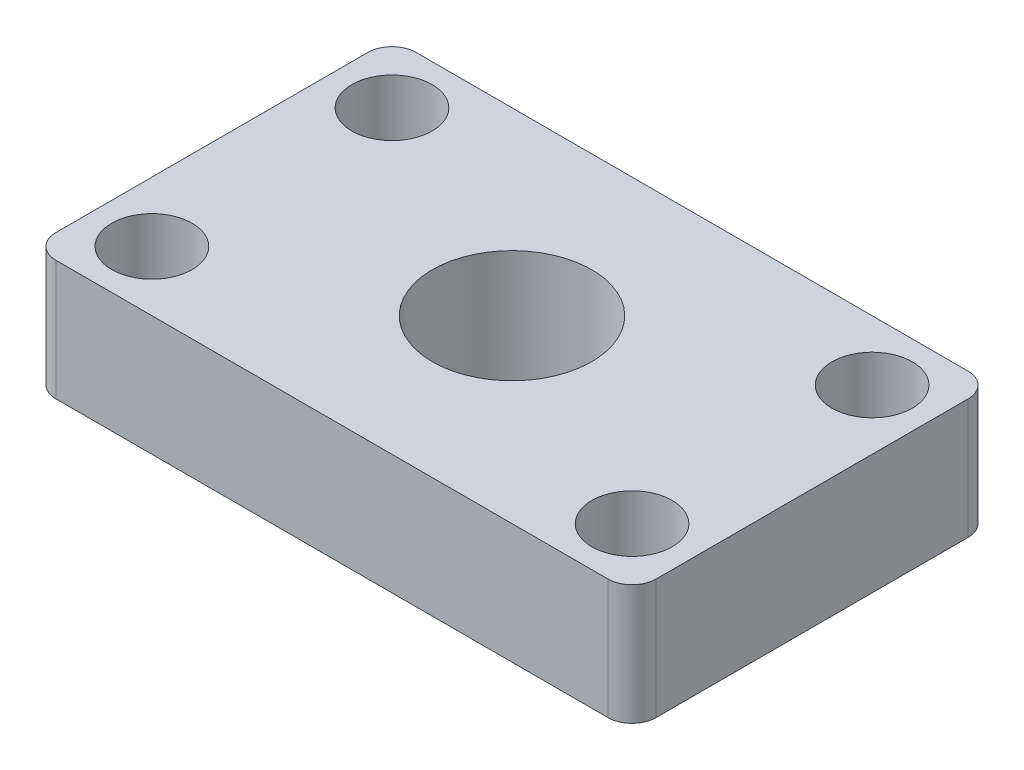
SolidWorks part; units mm, degrees
ref_plane "Front Plane" through (0, 0, 0) normal (0, 0, 1) x (1, 0, 0)
ref_plane "Top Plane" through (0, 0, 0) normal (0, 1, 0) x (1, 0, 0)
ref_plane "Right Plane" through (0, 0, 0) normal (1, 0, 0) x (0, 0, -1)
sketch "Sketch1" plane through (0, 0, 0) normal (0, 1, 0) x (1, 0, 0)
  line L0 (0, 0) -> (-20, 0) construction
  line L1 (-25, 15) -> (25, 15)
  line L2 (-25, 15) -> (-25, -15)
  line L3 (-25, -15) -> (25, -15)
  line L4 (25, 15) -> (25, -15)
  line L5 (-25, 15) -> (25, -15) construction
  line L6 (-25, -15) -> (25, 15) construction
  line L7 (-20, 0) -> (-20, 10) construction
  line L8 (-20, 10) -> (20, 10) construction
  line L9 (20, 10) -> (20, -10) construction
  line L10 (20, -10) -> (-20, -10) construction
  circle A0 centre (-20, 10) radius 3.35
  circle A1 centre (20, 10) radius 3.35
  circle A2 centre (-20, -10) radius 3.35
  circle A3 centre (20, -10) radius 3.35
  point P0 (0, 0)
extrude "Boss-Extrude2" add sketch "Sketch1" along normal blind 10
sketch "Sketch10" plane through (0, 0, -15) normal (0, 0, -1) x (-1, 0, 0)
  line L0 (-25, 10) -> (25, 0) construction
  line L1 (25, 0) -> (0, 5) construction
hole_wizard "#8-32 Tapped Hole3" positions "3DSketch2" profile "Sketch11" tap size "#8-32" standard "ANSI Inch"
sketch3d "3DSketch2"
  point P0 (0, 5, -15)
sketch "Sketch11" plane through (0, 5, -15) normal (1, 0, 0) x (0, 1, 0)
  line L0 (0, 0) -> (0, 6.0378)
  line L1 (0, 6.0378) -> (1.7272, 5)
  line L2 (1.7272, 5) -> (1.7272, 0)
  line L5 (1.7272, 0) -> (0, 0)
  line L10 (0, 6.0378) -> (-1.7272, 5) construction
  line L11 (0, -6.35) -> (0, 107.95) construction
  dimension "Tap Drill Dia." = 3.4544
  dimension "Tap Drill Depth" = 5
  dimension "Drill Angle" = 118
cosmetic thread "Hole Thread3" parameters "D1"=4, "D2"=4.1656
fillet "Fillet3" radius 2 3 edges at (-25, 5, -15) (25, 5, 15) (25, 5, -15)
fillet "Fillet4" radius 2 1 edges at (-25, 5, 15)
sketch "Sketch19" plane through (0, 0, 0) normal (0, -1, 0) x (-1, 0, 0)
  line L0 (-25, 0) -> (0, 0) construction
  line L1 (-25, -13) -> (-25, 13) construction
sketch "Sketch21" plane through (0, 10, 0) normal (0, 1, 0) x (1, 0, 0)
  line L0 (-25, 0) -> (0, 0) construction
  line L1 (-25, 13) -> (-25, -13) construction
hole_wizard "0.535-40 Tapped Hole2" positions "3DSketch11" profile "Sketch22" tap size "0.535-40" standard "ANSI Inch" end condition through all
sketch3d "3DSketch11"
  point P0 (0, 10, 0)
sketch "Sketch22" plane through (0, 10, 0) normal (1, 0, 0) x (0, 0, 1)
  line L0 (0, 0) -> (0, 10)
  line L1 (0, 10) -> (6.6421, 10)
  line L2 (6.6421, 10) -> (6.6421, 0)
  line L5 (6.6421, 0) -> (0, 0)
  line L11 (0, -6.35) -> (0, 107.95) construction
  dimension "Thru Tap Drill Dia." = 13.2842
  dimension "Thru Tap Drill Depth" = 10
cosmetic thread "Hole Thread6" parameters "D2"=13.589
